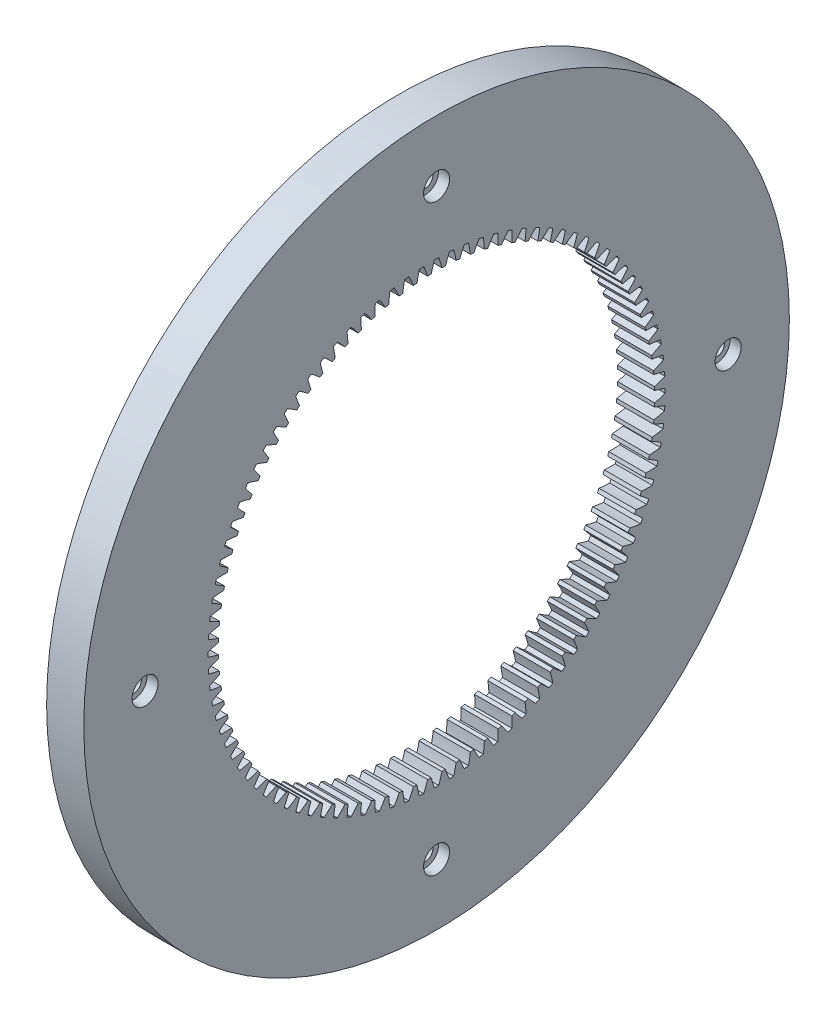
SolidWorks part; units mm, degrees
ref_plane "Plane1" through (0, 0, 0) normal (0, 0, 1) x (1, 0, 0)
ref_plane "Plane2" through (0, 0, 0) normal (0, 1, 0) x (1, 0, 0)
ref_plane "Plane3" through (0, 0, 0) normal (1, 0, 0) x (0, 0, -1)
sketch "HoldingSke" plane through (0, 0, 0) normal (0, 1, 0) x (1, 0, 0)
  line L0 (0, 0) -> (-0.0836, -0.7956)
  line L1 (-15, 0) -> (100, 0) construction
  line L2 (0, 0) -> (-2.1039, 2.3779)
  line L3 (0, 0) -> (-11.863, 4.5341)
  line L4 (0, 0) -> (-0.9027, 8.5887)
  line L5 (0, 0) -> (-23.7986, -8.8762)
  line L6 (0, 0) -> (-10.5278, -7.1032)
  line L7 (-2.1039, 2.3779) -> (3.3635, 27.1825)
  line L8 (-76.2, 3.6279) -> (-54.61, 3.6279)
  line L9 (-67.7845, 28.3722) -> (-49.3413, 33.142)
  line L10 (-76.2, 71.12) -> (104.1128, 71.12)
  line L11 (0, 0) -> (-10, 0)
  line L12 (-76.2, 101.6) -> (-76.155, 101.6)
  line L13 (24.9733, 27.94) -> (52.9518, 28.4284)
  line L14 (24.9733, 27.94) -> (24.9743, 27.94)
  line L15 (24.9733, 27.94) -> (100.4006, 29.5858)
  circle A0 centre (0, 0) radius 95
  circle A1 centre (0, 0) radius 12.7
  circle A2 centre (0, 0) radius 12.7
  dimension "Num_teeth" = 96
  dimension "Pitch_radius" = 180.3128
  dimension "Width" = 10
  dimension "Diameter" = 190
sketch "BasProSke" plane through (0, 0, 0) normal (0, 1, 0) x (1, 0, 0)
  line L0 (-10, 0) -> (60, 0) construction
  line L1 (0, 58.75) -> (0, 95)
  line L2 (0, 58.75) -> (10, 58.75)
  line L3 (10, 58.75) -> (10, 95)
  line L4 (10, 95) -> (0, 95)
  dimension "Thickness" = 10
  dimension "Diameter" = 190
revolve "Base-Revolve" add sketch "BasProSke" angle 360 about L0
sketch "TooCutSke" plane through (0, 0, 0) normal (1, 0, 0) x (0, 0, -1)
  line L3 (1.0942, 59.99) -> (1.0942, 53.6633) construction
  line L4 (0, 0) -> (0, 59.563) construction
  line L5 (0, 0) -> (-2.2356, 68.2909) construction
  line L6 (-27.6505, 51.4028) -> (36.112, 53.4902) construction
  circle A0 centre (0, 0) radius 60 construction
  circle A1 centre (0, 0) radius 61.5635 construction
  circle A2 centre (0, 0) radius 52.28 construction
  circle A3 centre (0, 0) radius 58.7246 construction
  arc A4 (1.4468, 58.7068) -> (0.5774, 61.5608) centre (-27.6505, 51.4028) ccw
  arc A5 (1.4468, 58.7068) -> (-1.4468, 58.7068) centre (0, 0) ccw
  arc A6 (0.5774, 61.5608) -> (-0.5774, 61.5608) centre (0, 0) ccw
  arc A7 (-0.5774, 61.5608) -> (-1.4468, 58.7068) centre (27.6505, 51.4028) ccw
extrude "ToothCut" cut sketch "TooCutSke" along normal through all
fillet "Breaks" [suppressed] radius 0.125
fillet "RootFillets" [suppressed] radius 0.3135
pattern_circular "TeethCuts" count 96 every 3.75 about axis through (-10, 0, 0) along (1, 0, 0) of "RootFillets", "Breaks", "ToothCut"
sketch "Sketch1" plane through (10, 0, 0) normal (1, 0, 0) x (0, 0, -1)
  circle A0 centre (0, 0) radius 78.5 construction
  circle A1 centre (0, 78.5) radius 2
  circle A2 centre (78.5, 0) radius 2
  circle A3 centre (0, -78.5) radius 2
  circle A4 centre (-78.5, 0) radius 2
  point P14 (0, 0)
  dimension "D1" = 157
  dimension "D2" = 4
  dimension "D3" = 4
extrude "Cut-Extrude1" cut sketch "Sketch1" against normal blind 10
sketch "Sketch2" plane through (10, 0, 0) normal (1, 0, 0) x (0, 0, -1)
  circle A0 centre (0, 78.5) radius 3.5
  circle A1 centre (78.5, 0) radius 3.5
  circle A2 centre (0, -78.5) radius 3.5
  circle A3 centre (-78.5, 0) radius 3.5
  point P12 (0, -1.1397)
  point P13 (0, 0)
  dimension "D1" = 7
  dimension "D2" = 4
extrude "Cut-Extrude2" cut sketch "Sketch2" against normal blind 3
equation "' \"Module@HoldingSke\" = 6.35"
equation "' \"Num_teeth@HoldingSke\" = 24"
equation "' \"Ap@HoldingSke\" =  14.5"
equation "' \"Ap@HoldingSke\" = 14.5"
equation "' \"Width@HoldingSke\" = 12"
equation "' \"Diameter@HoldingSke\" = 8 * 25.4"
equation "' \"Show_teeth@HoldingSke\" = 100"
equation "' \"Backlash@HoldingSke\" = 0.009 * 25.4"
equation "' \"Addendum_fac@HoldingSke\" = 1.0"
equation "' \"Dedendum_fac@HoldingSke\" = 1.25"
equation "' \"Dedendum_add@HoldingSke\" = 0.00005 * 25.4"
equation "' \"Clearance_fac@HoldingSke\" = 0.25"
equation "\"Pitch@HoldingSke\" = 1 / \"Module@HoldingSke\" "
equation "\"Overcut_dia@TooCutSke\" = (\"Num_teeth@HoldingSke\" - 2 * \"Addendum_fac@HoldingSke\") / \"Pitch@HoldingSke\" - 0.002 * 25.4"
equation "\"Pitch_dia@TooCutSke\" = \"Num_teeth@HoldingSke\" / \"Pitch@HoldingSke\""
equation "\"Base_dia@TooCutSke\" = \"Num_teeth@HoldingSke\" / \"Pitch@HoldingSke\" * cos((\"Ap@HoldingSke\"  * 3.14159265 / 180)) * 0.90"
equation "\"Root_dia@TooCutSke\" = \"Num_teeth@HoldingSke\"  / \"Pitch@HoldingSke\" + 2 *  \"Dedendum_fac@HoldingSke\"/ \"Pitch@HoldingSke\" + \"Dedendum_add@HoldingSke\" * 2"
equation "\"Half_ang@TooCutSke\" = 180 / \"Num_teeth@HoldingSke\""
equation "\"Half_CT@TooCutSke\" = \"Num_teeth@HoldingSke\" / \"Pitch@HoldingSke\" * sin((3.14159265 / 2 / \"Num_teeth@HoldingSke\")) / 2 + 10 * \"Backlash@HoldingSke\" / 4"
equation "\"Flank_rad@TooCutSke\" = \"Num_teeth@HoldingSke\" / \"Pitch@HoldingSke\" / 4"
equation "\"Radius@RootFillets\"= \"Clearance_fac@HoldingSke\" / \"Pitch@HoldingSke\" + \"Dedendum_add@HoldingSke\""
equation "\"Break_rad@Breaks\" = 0.02 / \"Pitch@HoldingSke\" * 5"
equation "\"Num_teeth@TeethCuts\" = int( \"Show_teeth@HoldingSke\" ) + 1"
equation "\"Num_teeth@TeethCuts\" = ((sgn( \"Num_teeth@TeethCuts\" - \"Num_teeth@HoldingSke\" )-1)*( \"Num_teeth@TeethCuts\" - \"Num_teeth@HoldingSke\" ))/-2+ \"Num_teeth@HoldingSke\""
equation "\"Num_teeth@TeethCuts\" = ((sgn( \"Num_teeth@TeethCuts\" - 2.0)+1)*( \"Num_teeth@TeethCuts\" - 2.0))/2 +2.0"
equation "\"Angle@TeethCuts\" = 360.0 / \"Num_teeth@HoldingSke\""
equation "\"Diameter@BasProSke\" = \"Num_teeth@HoldingSke\"  / \"Pitch@HoldingSke\" + 2 *  \"Dedendum_fac@HoldingSke\"/ \"Pitch@HoldingSke\" + \"Dedendum_add@HoldingSke\" * 2 + 0.002 * 25.4"
equation "\"Diameter@BasProSke\" = ((sgn( \"Diameter@BasProSke\"  - \"Diameter@HoldingSke\" )+1)*( \"Diameter@BasProSke\"  - \"Diameter@HoldingSke\" ))/2 + \"Diameter@HoldingSke\""
equation "\"Inside_diameter@BasProSke\" =  (\"Num_teeth@HoldingSke\" - 2 * \"Addendum_fac@HoldingSke\") / \"Pitch@HoldingSke\" "
equation "\"Thickness@BasProSke\"  = \"Width@HoldingSke\""
